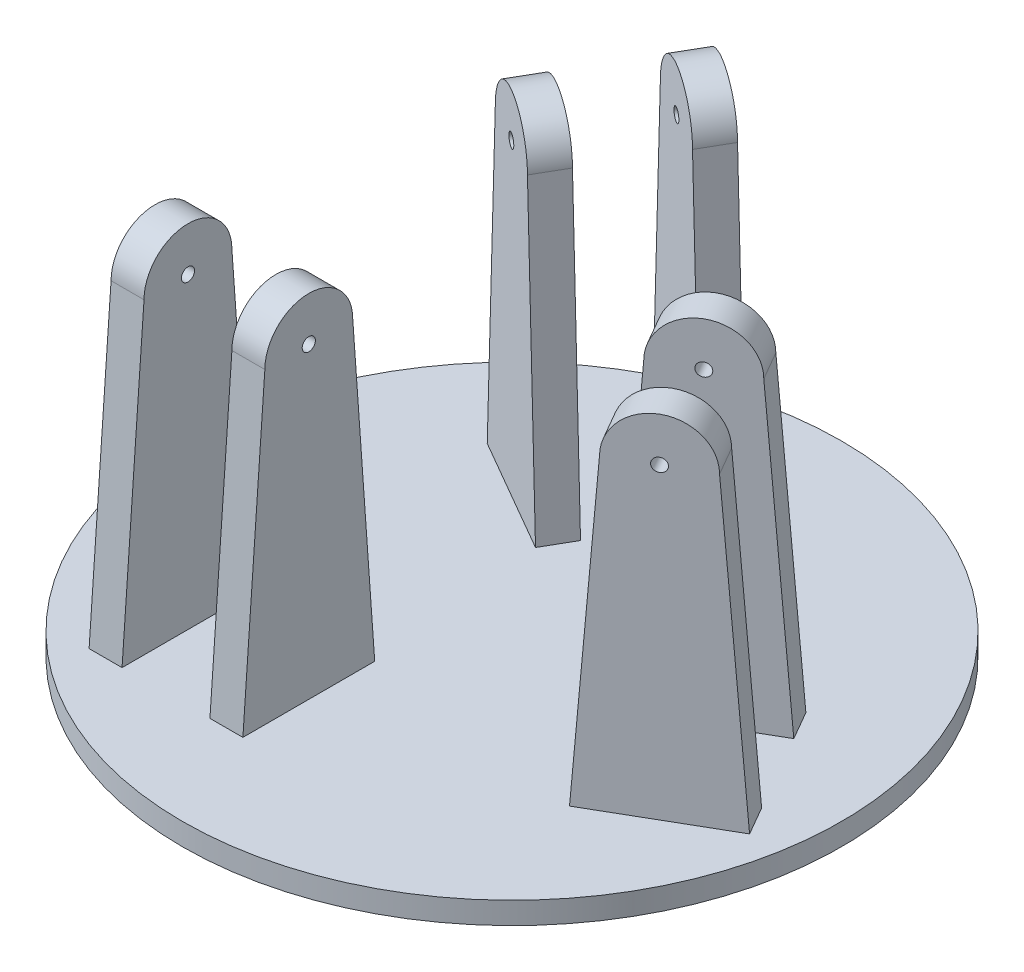
SolidWorks part; units mm, degrees
ref_plane "Front Plane" through (0, 0, 0) normal (0, 0, 1) x (1, 0, 0)
ref_plane "Top Plane" through (0, 0, 0) normal (0, 1, 0) x (1, 0, 0)
ref_plane "Right Plane" through (0, 0, 0) normal (1, 0, 0) x (0, 0, -1)
sketch "Sketch2" plane through (0, 0, 0) normal (0, 1, 0) x (1, 0, 0)
  circle A0 centre (0, 0) radius 75
  dimension "D1" = 150
extrude "Extrude1" add sketch "Sketch2" along normal blind 5
sketch "Sketch1" plane through (0, 0, 0) normal (0, 1, 0) x (1, 0, 0)
  line L0 (-44.6893, -36.5541) -> (-9.6893, -36.5541) construction
  line L1 (-9.3121, 56.9791) -> (-26.8121, 26.6682) construction
  line L2 (54.0014, -20.425) -> (36.5014, 9.8859) construction
  line L3 (0, 0) -> (-27.1893, -36.5541) construction
  line L4 (0, 0) -> (-18.0621, 41.8237) construction
  line L5 (0, 0) -> (45.2514, -5.2696) construction
  line L6 (-27.1893, -36.7902) -> (-27.1893, -16.2561) construction
  line L7 (-9.6893, -21.5541) -> (-17.1893, -21.5541)
  line L8 (-9.6893, -21.5541) -> (-9.6893, -51.5541)
  line L9 (-9.6893, -51.5541) -> (-17.1893, -51.5541)
  line L10 (-17.1893, -21.5541) -> (-17.1893, -51.5541)
  line L12 (-37.1893, -21.5541) -> (-37.1893, -51.5541)
  line L13 (-44.6893, -51.5541) -> (-37.1893, -51.5541)
  line L14 (-44.6893, -21.5541) -> (-44.6893, -51.5541)
  line L15 (-44.6893, -21.5541) -> (-37.1893, -21.5541)
  circle A0 centre (0, 0) radius 75 construction
  point P16 (-9.6893, -36.5541)
  dimension "D1" = 150
  dimension "D2" = 35
  dimension "D3" = 100
  dimension "D4" = 65.5
  dimension "D5" = 7.5
  dimension "D6" = 30
extrude "Extrude3" add sketch "Sketch1" along normal blind 80 from surface starting at face at (0, 5, 75)
sketch "Sketch3" plane through (0, 0, 0) normal (1, 0, 0) x (0, 0, -1)
  line L0 (-51.5541, 5) -> (-52.5541, 6)
  line L1 (-52.5541, 6) -> (-52.5541, 86)
  line L2 (-52.5541, 86) -> (-20.5541, 86)
  line L3 (-20.5541, 86) -> (-20.5541, 6)
  line L4 (-20.5541, 6) -> (-21.5541, 5)
  line L5 (-21.5541, 5) -> (-26.5541, 75)
  line L6 (-51.5541, 5) -> (-46.5541, 75)
  line L7 (-21.5541, 85) -> (-51.5541, 85) construction
  line L8 (-51.5541, 85) -> (-51.5541, 5) construction
  line L9 (-21.5541, 85) -> (-21.5541, 5) construction
  line L10 (75, 5) -> (-75, 5) construction
  arc A0 (-26.5541, 75) -> (-46.5541, 75) centre (-36.5541, 75) ccw
  circle A1 centre (-36.5541, 75) radius 1.5
  point P13 (-36.5541, 85)
  point P14 (-36.5541, 85)
  dimension "D1" = 10
  dimension "D7" = 3
  dimension "D2" = 1
  dimension "D3" = 1
  dimension "D4" = 1
  dimension "D5" = 1
  dimension "D6" = 1
extrude "Cut-Extrude1" cut sketch "Sketch3" against normal blind 55
ref_axis "Axis1" through (0, -3, 0) along (0, 1, 0)
pattern_circular "CirPattern1" count 3 over 360 about axis through (0, -3, 0) along (0, 1, 0) of "Extrude3", "Cut-Extrude1"
